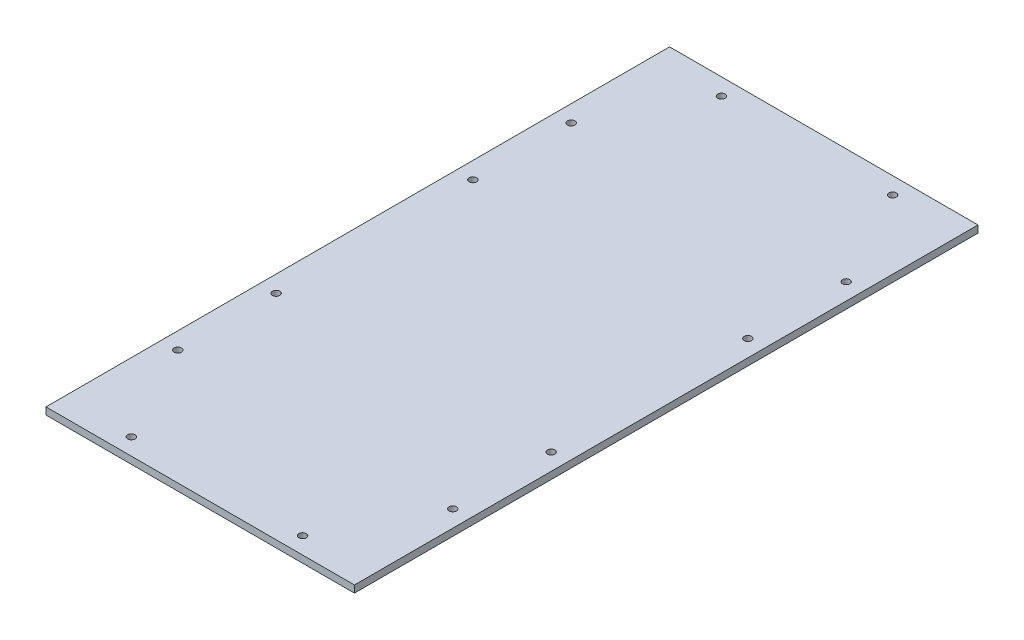
SolidWorks part; units mm, degrees
ref_plane "Front Plane" through (0, 0, 0) normal (0, 0, 1) x (1, 0, 0)
ref_plane "Top Plane" through (0, 0, 0) normal (0, 1, 0) x (1, 0, 0)
ref_plane "Right Plane" through (0, 0, 0) normal (1, 0, 0) x (0, 0, -1)
sketch "Sketch1" plane through (0, 0, 0) normal (0, 1, 0) x (1, 0, 0)
  line L0 (0, 139.7) -> (0, -139.7) construction
  line L1 (-69.1, 139.7) -> (69.1, 139.7)
  line L2 (-69.1, 139.7) -> (-69.1, -139.7)
  line L3 (-69.1, -139.7) -> (69.1, -139.7)
  line L4 (69.1, 139.7) -> (69.1, -139.7)
  line L5 (-69.1, 139.7) -> (69.1, -139.7) construction
  line L6 (-69.1, -139.7) -> (69.1, 139.7) construction
  line L7 (-61.6, 132.2) -> (61.6, 132.2) construction
  line L8 (-61.6, 132.2) -> (-61.6, -132.2) construction
  line L9 (-61.6, -132.2) -> (61.6, -132.2) construction
  line L10 (61.6, 132.2) -> (61.6, -132.2) construction
  line L11 (-61.6, 132.2) -> (61.6, -132.2) construction
  line L12 (-61.6, -132.2) -> (61.6, 132.2) construction
  line L13 (-69.1, 0) -> (69.1, 0) construction
  line L14 (-61.6, -132.2) -> (61.6, -132.2) construction
  circle A0 centre (-38.36, 132.2) radius 1.65
  circle A1 centre (-61.6, 88.1333) radius 1.65
  circle A2 centre (-61.6, 44.0667) radius 1.65
  circle A3 centre (61.6, 44.0667) radius 1.65
  circle A4 centre (61.6, 88.1333) radius 1.65
  circle A5 centre (38.36, 132.2) radius 1.65
  circle A6 centre (38.36, -132.2) radius 1.65
  circle A7 centre (61.6, -88.1333) radius 1.65
  circle A8 centre (61.6, -44.0667) radius 1.65
  circle A9 centre (-61.6, -44.0667) radius 1.65
  circle A10 centre (-61.6, -88.1333) radius 1.65
  circle A11 centre (-38.36, -132.2) radius 1.65
  point P0 (0, 0)
  point P6 (0, 0)
  dimension "D5" = 3.3
  dimension "D6" = 3.3
  dimension "D7" = 3.3
  dimension "D1" = 7.5
  dimension "D2" = 7.5
  dimension "D3" = 279.4
  dimension "D4" = 138.2
  dimension "D8" = 23.24
  dimension "D9" = 44.0667
  dimension "D10" = 44.0667
  dimension "D11" = 44.0667
extrude "Boss-Extrude1" add sketch "Sketch1" along normal blind 3.175
equation "\"D6@Sketch1\"=\"D5@Sketch1\""
equation "\"D7@Sketch1\"=\"D5@Sketch1\""
equation "\"D10@Sketch1\"=\"D9@Sketch1\""
